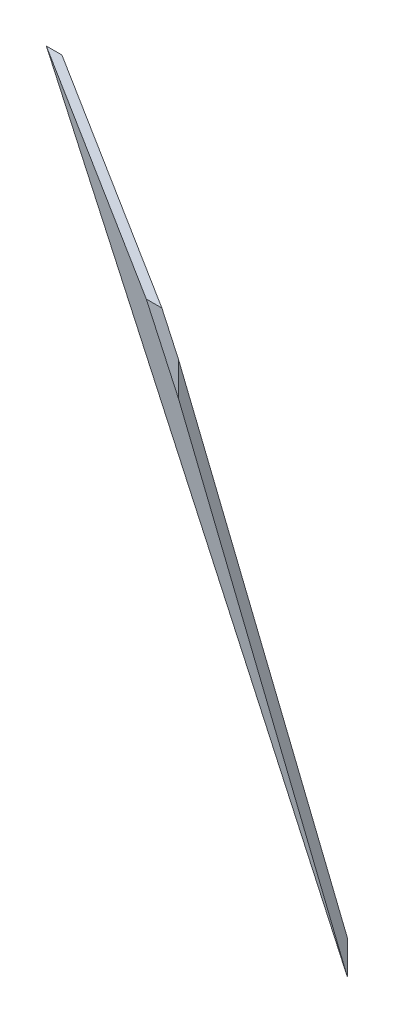
SolidWorks part; units mm, degrees
ref_plane "Plan de face" through (0, 0, 0) normal (0, 0, 1) x (1, 0, 0)
ref_plane "Plan de dessus" through (0, 0, 0) normal (0, 1, 0) x (1, 0, 0)
ref_plane "Plan de droite" through (0, 0, 0) normal (1, 0, 0) x (0, 0, -1)
sketch "Esquisse1" plane through (0, 0, 0) normal (0, 0, 1) x (1, 0, 0)
  line L0 (0, 0) -> (0, 815)
  line L1 (0, 815) -> (-374.0984, 815)
  line L2 (-374.0984, 815) -> (0, 0)
  line L3 (-374.0984, 815) -> (-420, 915) construction
  line L4 (-420, 915) -> (0, 915) construction
  line L5 (0, 915) -> (0, 815) construction
  dimension "D1" = 915
  dimension "D2" = 420
  dimension "D3" = 815
extrude "Boss.-Extru.1" add sketch "Esquisse1" against normal blind 210
sketch "Esquisse4" plane through (0, 815, 0) normal (0, 1, 0) x (1, 0, 0)
  line L0 (-40, 210) -> (-374.0984, 0)
  line L1 (-374.0984, 0) -> (-374.0984, 210)
  line L2 (-374.0984, 210) -> (-40, 210)
  line L3 (0, 210) -> (-374.0984, 210) construction
  line L4 (0, 210) -> (0, 0) construction
  dimension "D1" = 40
extrude "Enlèv. mat.-Extru.4" cut sketch "Esquisse4" against normal through all
ref_plane "Plan2" through (0, 0, 0) normal (-0.517, -0.2373, -0.8225) x (-0.856, 0.1433, 0.4967)
sketch "Esquisse5" plane through (0, 0, 0) normal (-0.517, -0.2373, -0.8225) x (-0.856, 0.1433, 0.4967)
  line L0 (437.0269, 783.0594) -> (0, 0)
  line L1 (0, 0) -> (-104.3076, 58.2143)
  line L2 (-104.3076, 58.2143) -> (12.4883, 841.2737)
  line L3 (12.4883, 841.2737) -> (46.7286, 841.2737)
  line L4 (46.7286, 841.2737) -> (437.0269, 783.0594)
extrude "Enlèv. mat.-Extru.5" cut sketch "Esquisse5" along normal through all
ref_plane "Plan3" through (5.1696, 2.3729, 8.2246) normal (-0.517, -0.2373, -0.8225) x (-0.856, 0.1433, 0.4967)
sketch "Esquisse6" plane through (5.1696, 2.3729, 8.2246) normal (-0.517, -0.2373, -0.8225) x (-0.856, 0.1433, 0.4967)
  line L0 (437.0269, 783.0594) -> (46.7286, 841.2737)
  line L1 (46.7286, 841.2737) -> (12.4883, 841.2737)
  line L2 (12.4883, 841.2737) -> (0, 757.5461)
  line L3 (0, 757.5461) -> (0, 0)
  line L4 (0, 0) -> (437.0269, 783.0594)
extrude "Enlèv. mat.-Extru.6" cut sketch "Esquisse6" against normal through all
sketch "Esquisse7" plane through (5.1696, 2.3729, 8.2246) normal (0.517, 0.2373, 0.8225) x (0.856, -0.1433, -0.4967)
  line L4 (-45.7861, 173.2665) -> (-36.0392, 175.8023)
  line L5 (-323.6724, 767.165) -> (-348.7583, 716.1284)
  line L8 (-36.0392, 155.8023) -> (-36.0392, 790.2313)
  line L9 (-36.0392, 790.2313) -> (-46.2586, 808.5422)
  line L10 (-46.2586, 808.5422) -> (-373.1253, 759.789)
  line L11 (-373.1253, 759.789) -> (-36.0392, 155.8023)
  line L12 (-36.0392, 175.8023) -> (-36.0392, 790.2313)
  line L13 (-36.0392, 790.2313) -> (-46.2586, 808.5422)
  line L14 (-46.2586, 808.5422) -> (-323.6724, 767.165)
  line L15 (-348.7583, 716.1284) -> (-45.7861, 173.2665)
  dimension "D1" = 30
extrude "Enlèv. mat.-Extru.7" cut sketch "Esquisse7" against normal blind 5
chamfer "Chanfrein1" distance 5 angle 45 6 edges at (-32.4367, 174.7438, -23.9491) (-166.2816, 456.7265, -21.177) (-285.218, 761.9497, -34.4811) (-155.747, 784.6704, -122.4164) (-32.639, 775.1415, -197.0476) (-28.265, 470.4381, -111.8844)
mirror "Symétrie1" about plane through (0, 0, -210) normal (0, 0, -1) of bodies 108
sketch "Esquisse8" plane through (0, 815, 0) normal (0, 1, 0) x (1, 0, 0)
  line L0 (-20.6563, 210) -> (184.8121, 210)
  line L1 (-20.6563, 210) -> (-435.3962, 210)
  line L2 (-20.6563, 210) -> (-20.6563, -49.5731) construction
  line L3 (-20.6563, -49.5731) -> (-435.3962, -49.5731)
  line L4 (-435.3962, 210) -> (-435.3962, -49.5731)
  line L5 (184.8121, 210) -> (184.8121, -49.5731)
  line L6 (184.8121, -49.5731) -> (-20.6563, -49.5731)
extrude "Enlèv. mat.-Extru.8" cut sketch "Esquisse8" against normal through all
